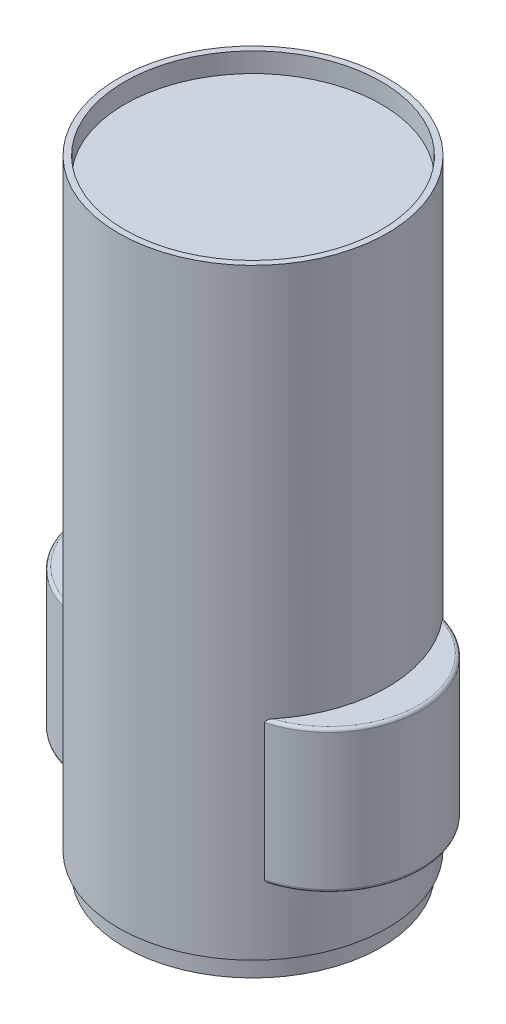
SolidWorks part; units mm, degrees
material "Al 6061-T6/T651"
ref_plane "Front Plane" through (0, 0, 0) normal (0, 0, 1) x (1, 0, 0)
ref_plane "Top Plane" through (0, 0, 0) normal (0, 1, 0) x (1, 0, 0)
ref_plane "Right Plane" through (0, 0, 0) normal (1, 0, 0) x (0, 0, -1)
sketch "Sketch1" plane through (0, 0, 0) normal (1, 0, 0) x (0, 0, -1)
  line L0 (0, 0) -> (-42.5, 0)
  line L1 (-42.5, 0) -> (-42.5, 6.5)
  line L2 (-42.5, 6.5) -> (-44.5, 6.5)
  line L3 (-44.5, 6.5) -> (-44.5, 205.8)
  line L4 (-44.5, 205.8) -> (-42.5, 205.8)
  line L5 (-42.5, 205.8) -> (-42.5, 199.3)
  line L6 (-42.5, 199.3) -> (0, 199.3)
  line L7 (0, 199.3) -> (0, 0)
  line L8 (0, 29.9719) -> (0, 40.8779) construction
  dimension "D1" = 89
  dimension "D2" = 6.5
  dimension "D3" = 85
  dimension "D4" = 199.3
revolve "Revolve1" add sketch "Sketch1" angle 360 about L7
ref_plane "Plane1" through (0, 28.5, 0) normal (0, -1, 0) x (1, 0, 0)
sketch "Sketch2" plane through (0, 28.5, 0) normal (0, -1, 0) x (1, 0, 0)
  line L0 (25.15, 0) -> (-25.15, 0) construction
  arc A0 (0, -17.4309) -> (0, 17.4309) centre (25.15, 0) ccw
  arc A1 (0, 17.4309) -> (0, -17.4309) centre (-25.15, 0) ccw
  dimension "D2" = 61.2
  dimension "D1" = 50.3
extrude "Extrude1" add sketch "Sketch2" against normal blind 47.07
sketch "Sketch3" plane through (0, 75.57, 0) normal (0, 1, 0) x (-1, 0, 0)
  line L0 (48.03, 5) -> (48.03, -5)
  line L2 (48.03, 0) -> (20.5452, 0) construction
  arc A0 (48.03, -5) -> (44.9068, -5.0935) centre (46.467, -5) cw
  arc A2 (44.9068, 5.0935) -> (48.03, 5) centre (46.467, 5) cw
  arc A4 (44.9068, -5.0935) -> (44.2097, -5.0746) centre (44.5574, -5.1145) ccw
  circle A5 centre (0, 0) radius 44.5 construction
  arc A6 (44.2097, -5.0746) -> (44.2097, 5.0746) centre (0, 0) ccw
  arc A7 (44.9068, 5.0935) -> (44.2097, 5.0746) centre (44.5574, 5.1145) cw
  dimension "D2" = 10
  dimension "D3" = 1.563
  dimension "D4" = 0.7
  dimension "D1" = 48.03
extrude "Extrude2" add sketch "Sketch3" along normal blind 100
fillet "Fillet1" radius 1 4 edges at (55.75, 28.5, 0) (55.75, 75.57, 0) (-55.75, 28.5, 0) (-55.75, 75.57, 0)
